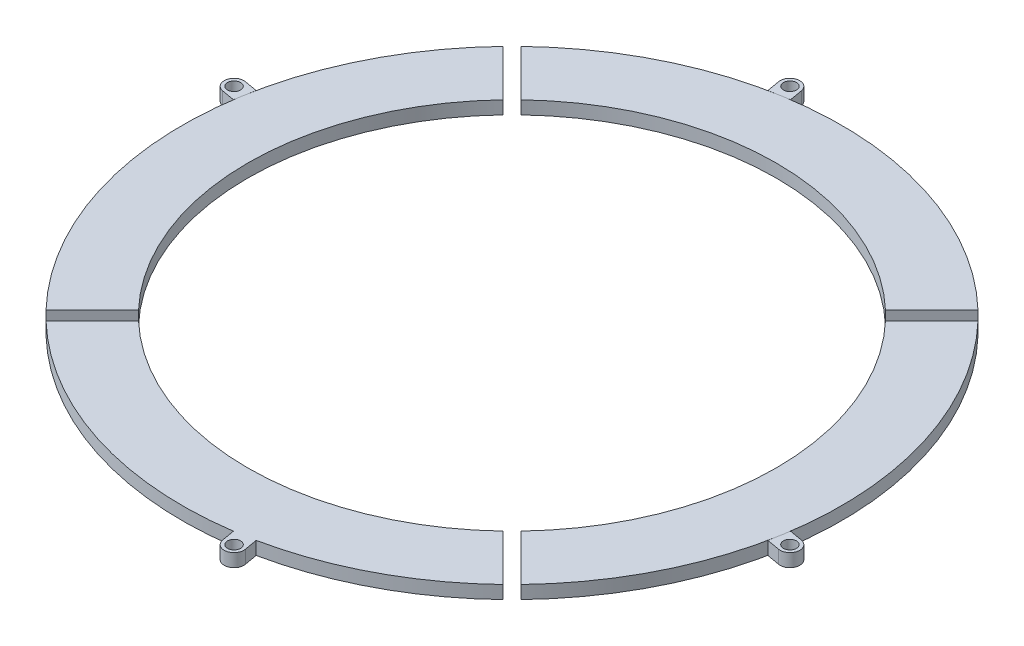
SolidWorks part; units mm, degrees
ref_plane "前视基准面" through (0, 0, 0) normal (0, 0, 1) x (1, 0, 0)
ref_plane "上视基准面" through (0, 0, 0) normal (0, 1, 0) x (1, 0, 0)
ref_plane "右视基准面" through (0, 0, 0) normal (1, 0, 0) x (0, 0, -1)
sketch "草图1" plane through (0, 0, 0) normal (0, 1, 0) x (1, 0, 0)
  line L0 (0, 28.5318) -> (0, -43.5615) construction
  line L1 (-12.686, 12.686) -> (30.0127, -30.0127) construction
  line L2 (0.7071, -0.7071) -> (71.4178, 70.0036)
  line L3 (71.4178, 70.0036) -> (70.0036, 71.4178)
  line L4 (70.0036, 71.4178) -> (-0.7071, 0.7071)
  line L5 (-0.7071, 0.7071) -> (0.7071, -0.7071)
  line L6 (0.7071, 0.7071) -> (-0.7071, -0.7071)
  line L7 (-0.7071, -0.7071) -> (70.0036, -71.4178)
  line L8 (70.0036, -71.4178) -> (71.4178, -70.0036)
  line L9 (71.4178, -70.0036) -> (0.7071, 0.7071)
  line L10 (0.7071, -0.7071) -> (-0.7071, 0.7071)
  line L11 (-0.7071, 0.7071) -> (-71.4178, -70.0036)
  line L12 (-71.4178, -70.0036) -> (-70.0036, -71.4178)
  line L13 (-70.0036, -71.4178) -> (0.7071, -0.7071)
  line L14 (-0.7071, -0.7071) -> (0.7071, 0.7071)
  line L15 (0.7071, 0.7071) -> (-70.0036, 71.4178)
  line L16 (-70.0036, 71.4178) -> (-71.4178, 70.0036)
  line L17 (-71.4178, 70.0036) -> (-0.7071, -0.7071)
  circle A0 centre (0, 0) radius 40.4
  circle A1 centre (0, 0) radius 50.4
  point P10 (0, 0)
  point P28 (0, 0)
  dimension "D2" = 80.8
  dimension "D3" = 100.8
  dimension "D1" = 45
  dimension "D4" = 100
  dimension "D5" = 2
  dimension "D6" = 4
extrude "凸台-拉伸1" add sketch "草图1" along normal blind 2 contours L17 A1 L11 A0 | L4 A1 L15 A0 | L9 A1 L2 A0 | L13 A1 L7 A0 region at (41.2874, 0, 0) region at (0, 0, 41.2874) region at (0, 0, -41.2874) region at (-41.2874, 0, 0)
sketch "草图2" plane through (0, 0, 0) normal (0, -1, 0) x (1, 0, 0)
  line L2 (0, 0) -> (9.0992, 51.6039) construction
  line L3 (10.2252, 49.3519) -> (7.2708, 49.8728)
  line L4 (8.3898, 8.3898) -> (0, 0) construction
  line L5 (27.8513, -29.2655) -> (29.2655, -27.8513) construction
  line L9 (0, 0) -> (10.8745, -10.8745) construction
  line L10 (7.2708, 49.8728) -> (7.622, 51.8644)
  line L17 (27.8513, 29.2655) -> (29.2655, 27.8513) construction
  line L18 (10.2252, 49.3519) -> (10.5764, 51.3435)
  line L19 (49.3519, 10.2252) -> (51.3435, 10.5764)
  line L20 (49.8728, 7.2708) -> (51.8644, 7.622)
  line L21 (49.3519, 10.2252) -> (49.8728, 7.2708)
  line L22 (-49.3519, -10.2252) -> (-51.3435, -10.5764)
  line L23 (-49.8728, -7.2708) -> (-51.8644, -7.622)
  line L24 (-49.3519, -10.2252) -> (-49.8728, -7.2708)
  line L25 (-10.2252, -49.3519) -> (-7.2708, -49.8728)
  line L26 (-7.2708, -49.8728) -> (-7.622, -51.8644)
  line L27 (-10.2252, -49.3519) -> (-10.5764, -51.3435)
  arc A2 (34.9241, 36.3383) -> (-34.9241, 36.3383) centre (0, 0) ccw construction
  arc A6 (-27.8513, -29.2655) -> (27.8513, -29.2655) centre (0, 0) ccw construction
  arc A7 (-27.8513, -29.2655) -> (27.8513, -29.2655) centre (0, 0) ccw construction
  arc A8 (34.9241, 36.3383) -> (-34.9241, 36.3383) centre (0, 0) ccw construction
  arc A9 (10.5764, 51.3435) -> (7.622, 51.8644) centre (9.0992, 51.6039) ccw
  circle A10 centre (9.0992, 51.6039) radius 1
  circle A11 centre (51.6039, 9.0992) radius 1
  arc A12 (51.3435, 10.5764) -> (51.8644, 7.622) centre (51.6039, 9.0992) cw
  circle A13 centre (-51.6039, -9.0992) radius 1
  arc A14 (-51.3435, -10.5764) -> (-51.8644, -7.622) centre (-51.6039, -9.0992) cw
  arc A15 (-10.5764, -51.3435) -> (-7.622, -51.8644) centre (-9.0992, -51.6039) ccw
  circle A16 centre (-9.0992, -51.6039) radius 1
  point P2 (0, 0)
  point P7 (0, 0)
  point P9 (9.0588, 51.375)
  dimension "D1" = 2
  dimension "D4" = 52.4
  dimension "D2" = 1.5
  dimension "D3" = 35
extrude "凸台-拉伸2" add sketch "草图2" against normal up to surface (2 mm away) up to face at (0, 2, 39.1009)
